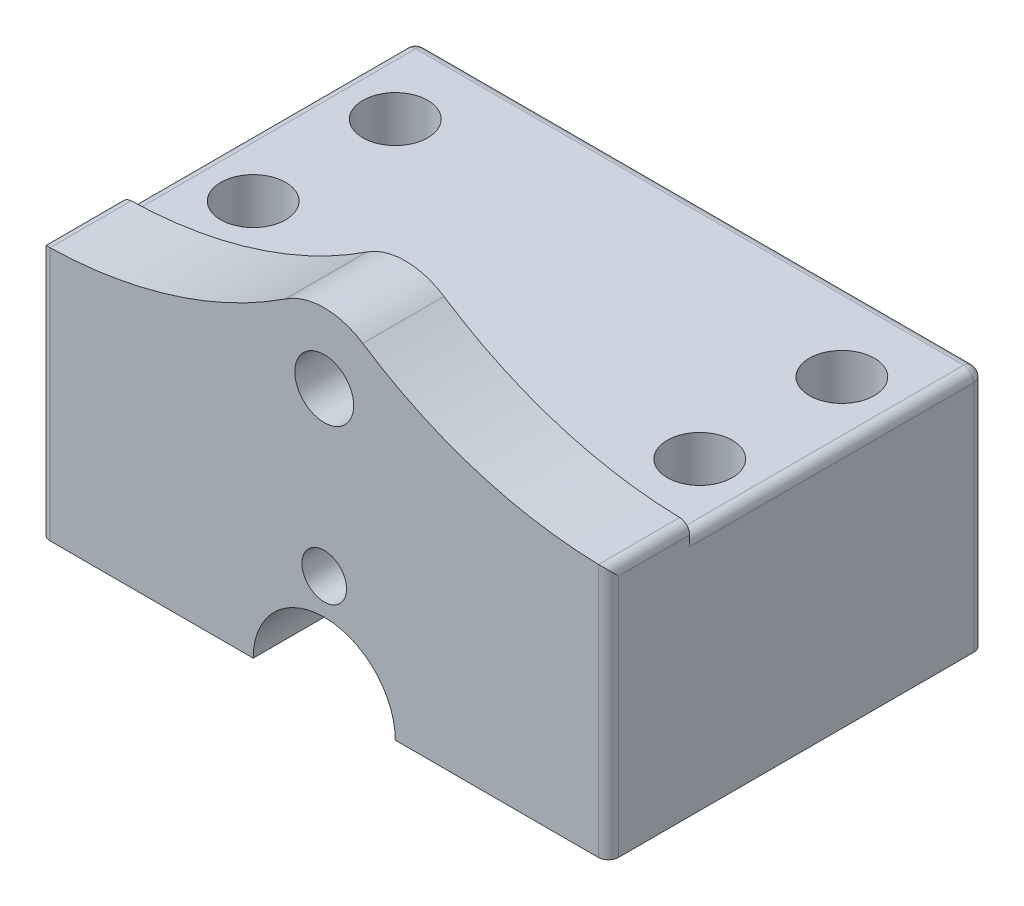
SolidWorks part; units mm, degrees
material "ABS"
ref_plane "Front Plane" through (0, 0, 0) normal (0, 0, 1) x (1, 0, 0)
ref_plane "Top Plane" through (0, 0, 0) normal (0, 1, 0) x (1, 0, 0)
ref_plane "Right Plane" through (0, 0, 0) normal (1, 0, 0) x (0, 0, -1)
sketch "Sketch1" plane through (0, 0, 0) normal (0, 0, 1) x (1, 0, 0)
  line L0 (-8, 0) -> (-14, 0)
  line L1 (-14, 0) -> (-14, 12)
  line L2 (-14, 12) -> (14, 12)
  line L3 (14, 12) -> (14, 0)
  line L4 (14, 0) -> (8, 0)
  line L5 (0, 0) -> (0, 8) construction
  arc A0 (8, 0) -> (-8, 0) centre (0, 0) ccw
  dimension "D1" = 16
  dimension "D2" = 6
  dimension "D3" = 4
extrude "Boss-Extrude1" add sketch "Sketch1" against normal blind 15
sketch "Sketch2" plane through (0, 0, 0) normal (0, -1, 0) x (1, 0, 0)
  line L0 (-11, 0) -> (-11, -15) construction
  line L1 (-14, 0) -> (-8, 0) construction
  line L2 (-14, -15) -> (-8, -15) construction
  line L3 (0, 0) -> (0, -15) construction
  line L4 (8, 0) -> (-8, 0) construction
  line L5 (-8, -15) -> (8, -15) construction
  point P6 (-11, -4)
  point P7 (-11, -11)
  point P14 (11, -11)
  point P15 (11, -4)
  dimension "D1" = 4
  dimension "D2" = 4
hole_wizard "M3 Clearance Hole1" positions "Sketch3" profile "Sketch4" hole size "M3" standard "ANSI Metric" end condition through all
sketch "Sketch3" plane through (0, 0, 0) normal (0, -1, 0) x (-1, 0, 0)
  point P0 (11, 11)
  point P3 (11, 4)
  point P6 (-11, 11)
  point P9 (-11, 4)
sketch "Sketch4" plane through (-11, 0, -11) normal (1, 0, 0) x (0, 0, -1)
  line L0 (0, 0) -> (0, 12)
  line L1 (0, 12) -> (1.6, 12)
  line L2 (1.6, 12) -> (1.6, 0)
  line L5 (1.6, 0) -> (0, 0)
  line L11 (0, -6.35) -> (0, 107.95) construction
  dimension "Thru Hole Dia." = 3.2
  dimension "Thru Hole Depth" = 12
sketch "Sketch5" plane through (0, 0, 0) normal (0, 0, 1) x (1, 0, 0)
  line L0 (-3.5, 0) -> (-14, 0)
  line L1 (-14, 0) -> (-14, 12)
  line L2 (-14, 12) -> (14, 12)
  line L3 (14, 12) -> (14, 0)
  line L4 (14, 0) -> (3.5, 0)
  arc A0 (3.5, 0) -> (-3.5, 0) centre (0, 0) ccw
  point P1 (0, 5.25)
  dimension "D1" = 7
  dimension "D2" = 5.25
extrude "Boss-Extrude2" add sketch "Sketch5" along normal blind 3.5
hole_wizard "M2 Clearance Hole2" positions "Sketch6" profile "Sketch7" hole size "M2" standard "ANSI Metric" end condition through all
sketch "Sketch6" plane through (0, 0, 3.5) normal (0, 0, 1) x (1, 0, 0)
  point P0 (0, 5.25)
sketch "Sketch7" plane through (0, 5.25, 3.5) normal (1, 0, 0) x (0, -1, 0)
  line L0 (0, 0) -> (0, 18.5)
  line L1 (0, 18.5) -> (1.1, 18.5)
  line L2 (1.1, 18.5) -> (1.1, 0)
  line L5 (1.1, 0) -> (0, 0)
  line L11 (0, -6.35) -> (0, 107.95) construction
  dimension "Thru Hole Dia." = 2.2
  dimension "Thru Hole Depth" = 18.5
sketch "Sketch8" plane through (0, 0, 3.5) normal (0, 0, 1) x (1, 0, 0)
  line L1 (-14, 12) -> (14, 12)
  line L2 (0, 13.25) -> (0, 0) construction
  line L3 (-14, 12) -> (-14, 12.5)
  line L4 (-14, 12.5) -> (0, 12.5) construction
  line L5 (14, 12) -> (14, 12.5)
  circle A0 centre (0, 13.25) radius 1.45
  arc A2 (1.8991, 16.1303) -> (-1.8991, 16.1303) centre (0, 13.25) ccw
  arc A5 (-14, 12.5) -> (-1.8991, 16.1303) centre (-14, 34.4833) ccw
  arc A6 (14, 12.5) -> (1.8991, 16.1303) centre (14, 34.4833) cw
  line M11 (14, 12) -> (-14, 12)
  dimension "D2" = 2.9
  dimension "D3" = 2
  dimension "D1" = 13.25
  dimension "D4" = 0.5
extrude "Boss-Extrude3" add sketch "Sketch8" against normal blind 4 contours L5 A6 A2 A5 L3 L1 A0 M11 | A0 region at (-13.7161, 12.25, 3.5) region at (0, 13.2913, 3.5)
extrude "Cut-Extrude1" cut sketch "Sketch8<3>" against normal offset from surface (3 mm away) 1 contours A0 | L1 A0 region at (0, 13.2913, 3.5) region at (0, 11.9195, 3.5) up to face at (0, 13.3424, -0.5)
sketch "Sketch8<3>" plane through (0, 0, 3.5) normal (0, 0, 1) x (1, 0, 0) same geometry as "Sketch8"
sketch "Sketch9" plane through (0, 0, -15) normal (0, 0, -1) x (-1, 0, 0)
  line L0 (-9, 0) -> (-11, 0)
  line L1 (9, 0) -> (11, 0)
  arc A0 (9, 0) -> (-9, 0) centre (0, 0) ccw
  arc A1 (11, 0) -> (-11, 0) centre (0, 0) ccw
  arc A2 (-9, 0) -> (9, 0) centre (0, 0) ccw construction
  arc A3 (-11, 0) -> (11, 0) centre (0, 0) ccw construction
  dimension "D1" = 18
  dimension "D2" = 2
extrude "Boss-Extrude4" [suppressed] add sketch "Sketch9" along normal blind 13
fillet "Fillet3" radius 0.5 9 edges at (14, 12, -7.75) (14, 12.5, 1.5) (-14, 12, -7.75) (-14, 12.5, 1.5) (14, 6, -15) (14, 6.25, 3.5) (-14, 6.25, 3.5) (-14, 6, -15) (0, 12, -15)
sketch "Sketch10" plane through (0, 12, 0) normal (0, 1, 0) x (1, 0, 0)
  line L0 (-13.5, 15) -> (13.5, 15) construction
  line L1 (-3.5, 19) -> (3.5, 19)
  line L2 (-3.5, 19) -> (-3.5, 15)
  line L3 (-3.5, 15) -> (3.5, 15)
  line L4 (3.5, 19) -> (3.5, 15)
  line L5 (0, 0) -> (0, 19) construction
  dimension "D1" = 7
  dimension "D2" = 4
extrude "Cut-Extrude2" [suppressed] cut sketch "Sketch10" against normal through all
fillet "Fillet4" [suppressed] radius 0.5
sketch "Sketch11" plane through (0, 0, -15) normal (0, 0, -1) x (-1, 0, 0)
  circle A0 centre (0, 0) radius 8.1
  arc A1 (8, 0) -> (-8, 0) centre (0, 0) ccw construction
  dimension "D1" = 0.1
extrude "Cut-Extrude3" cut sketch "Sketch11" against normal up to surface (15 mm away) up to face at (1.1, 5.25, 0)
